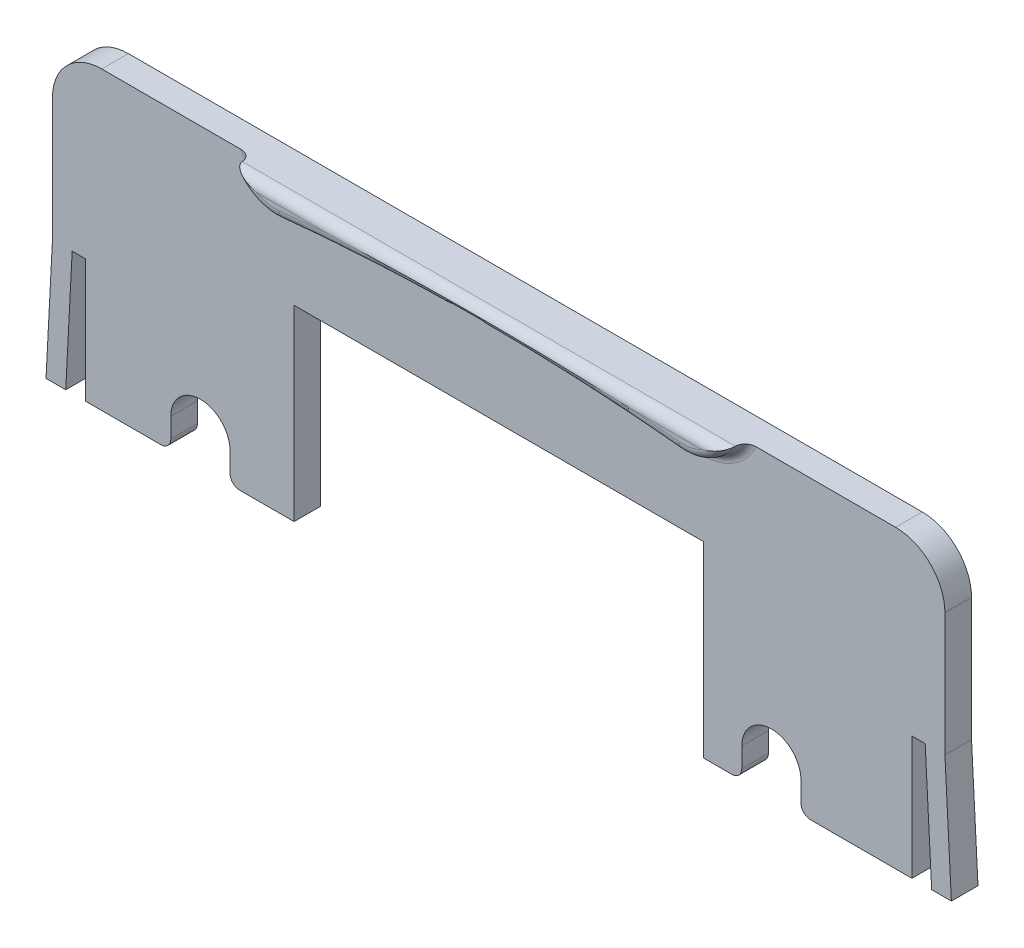
SolidWorks part; units mm, degrees
material "Esun Hard Tough Resin"
ref_plane "Front Plane" through (0, 0, 0) normal (0, 0, 1) x (1, 0, 0)
ref_plane "Top Plane" through (0, 0, 0) normal (0, 1, 0) x (1, 0, 0)
ref_plane "Right Plane" through (0, 0, 0) normal (1, 0, 0) x (0, 0, -1)
sketch "Sketch1" plane through (0, 0, 0) normal (0, 0, 1) x (1, 0, 0)
  line L0 (0, 5.5) -> (0, 0) construction
  line L1 (-20.75, -5.5) -> (20.75, -5.5)
  line L2 (-45.25, -5.5) -> (-45.25, 5.5)
  line L3 (-45.25, 5.5) -> (45.25, 5.5)
  line L4 (45.25, -5.5) -> (45.25, 5.5)
  line L5 (-45.25, -5.5) -> (45.25, 5.5) construction
  line L6 (-45.25, 5.5) -> (45.25, -5.5) construction
  line L8 (45.25, -5.5) -> (45.25, -24.5)
  line L9 (45.25, -24.5) -> (20.75, -24.5)
  line L10 (20.75, -5.5) -> (20.75, -24.5)
  line L11 (-20.75, -5.5) -> (-20.75, -24.5)
  line L12 (-45.25, -24.5) -> (-20.75, -24.5)
  line L13 (-45.25, -5.5) -> (-45.25, -24.5)
  point P0 (0, 0)
  dimension "D1" = 90.5
  dimension "D2" = 24.5
  dimension "D3" = 19
  dimension "D4" = 11
extrude "Boss-Extrude1" add sketch "Sketch1" against normal blind 2.7
fillet "Fillet1" radius 5 2 edges at (-45.25, 5.5, -1.35) (45.25, 5.5, -1.35)
sketch "Sketch2" plane through (0, 0, 0) normal (0, 0, 1) x (1, 0, 0)
  line L0 (40.25, 5.5) -> (-40.25, 5.5) construction
  line L1 (-25, 5.5) -> (25, 5.5)
  line L2 (-25, 5.5) -> (-25, 2.5)
  line L4 (25, 5.5) -> (25, 2.5)
  arc A0 (25, 2.5) -> (-25, 2.5) centre (0, -195.9313) ccw
  dimension "D3" = 200
  dimension "D1" = 3
  dimension "D2" = 50
extrude "Boss-Extrude2" add sketch "Sketch2" along normal blind 2
fillet "Fillet2" radius 5 2 edges at (-25, 2.5, 1) (25, 2.5, 1)
fillet "Fillet3" radius 1 7 edges at (22.9495, 3.5658, 0) (0, 4.0687, 0) (-22.9495, 3.5658, 0) (22.9495, 3.5658, 2) (0, 4.0687, 2) (-22.9495, 3.5658, 2) (0, 5.5, 2)
sketch "Sketch3" plane through (0, 0, 0) normal (0, 0, 1) x (1, 0, 0)
  line L0 (-45.25, -24.5) -> (-20.75, -24.5) construction
  line L1 (-1.3, 0) -> (-1.3, -5.5) construction
  line L2 (-30.25, -24.5) -> (-30.25, -21.5) construction
  line L3 (-20.75, -5.5) -> (20.75, -5.5) construction
  line L4 (-33.25, -24.5) -> (-33.25, -21.5)
  line L5 (-27.25, -24.5) -> (-27.25, -21.5)
  line L6 (27.65, -24.5) -> (27.65, -21.5) construction
  line L7 (30.65, -24.5) -> (30.65, -21.5)
  line L8 (24.65, -24.5) -> (24.65, -21.5)
  arc A2 (-33.25, -24.5) -> (-27.25, -24.5) centre (-30.25, -24.5) ccw
  arc A3 (-27.25, -21.5) -> (-33.25, -21.5) centre (-30.25, -21.5) ccw
  arc A4 (30.65, -24.5) -> (24.65, -24.5) centre (27.65, -24.5) cw
  arc A5 (24.65, -21.5) -> (30.65, -21.5) centre (27.65, -21.5) cw
  point P6 (-30.25, -23)
  point P10 (27.65, -23)
  point P11 (0, -5.5)
  dimension "D1" = 57.9
  dimension "D4" = 3
  dimension "D3" = 1.3
  dimension "D5" = 3
extrude "Fastener holes" cut sketch "Sketch3" against normal through all
fillet "Fillet4" radius 1 4 edges at (30.65, -24.5, -1.35) (24.65, -24.5, -1.35) (-27.25, -24.5, -1.35) (-33.25, -24.5, -1.35)
sketch "Sketch4" plane through (0, 0, 0) normal (0, 0, 1) x (1, 0, 0)
  line L0 (45.25, -12) -> (45.9051, -24.5)
  line L1 (45.25, -24.5) -> (45.25, 0.5) construction
  line L2 (45.9051, -24.5) -> (45.25, -24.5)
  line L3 (45.25, -12) -> (45.25, -24.5)
  line L4 (0, 0) -> (0, -5.5) construction
  line L5 (-20.75, -5.5) -> (20.75, -5.5) construction
  line L6 (-45.25, -12) -> (-45.25, -24.5)
  line L7 (-45.9051, -24.5) -> (-45.25, -24.5)
  line L8 (-45.25, -12) -> (-45.9051, -24.5)
  dimension "D1" = 3
extrude "Wedge" add sketch "Sketch4" against normal up to surface (2.7 mm away) up to face at (-0.7091, -16.7162, -2.7)
sketch "Sketch5" plane through (0, 0, 0) normal (0, 0, 1) x (1, 0, 0)
  line L0 (43.9051, -24.5) -> (43.25, -12)
  line L1 (31.65, -24.5) -> (45.9051, -24.5) construction
  line L2 (43.25, -12) -> (41.9051, -12)
  line L3 (41.9051, -12) -> (41.9051, -24.5)
  line L4 (41.9051, -24.5) -> (43.9051, -24.5)
  line L5 (45.9051, -24.5) -> (45.25, -12) construction
  line L6 (0, 0) -> (0, -5.5) construction
  line L7 (-20.75, -5.5) -> (20.75, -5.5) construction
  line L8 (-41.9051, -24.5) -> (-43.9051, -24.5)
  line L9 (-41.9051, -12) -> (-41.9051, -24.5)
  line L10 (-43.25, -12) -> (-41.9051, -12)
  line L11 (-43.9051, -24.5) -> (-43.25, -12)
  dimension "D1" = 2
  dimension "D2" = 2
extrude "Cut-Extrude2" cut sketch "Sketch5" against normal through all
